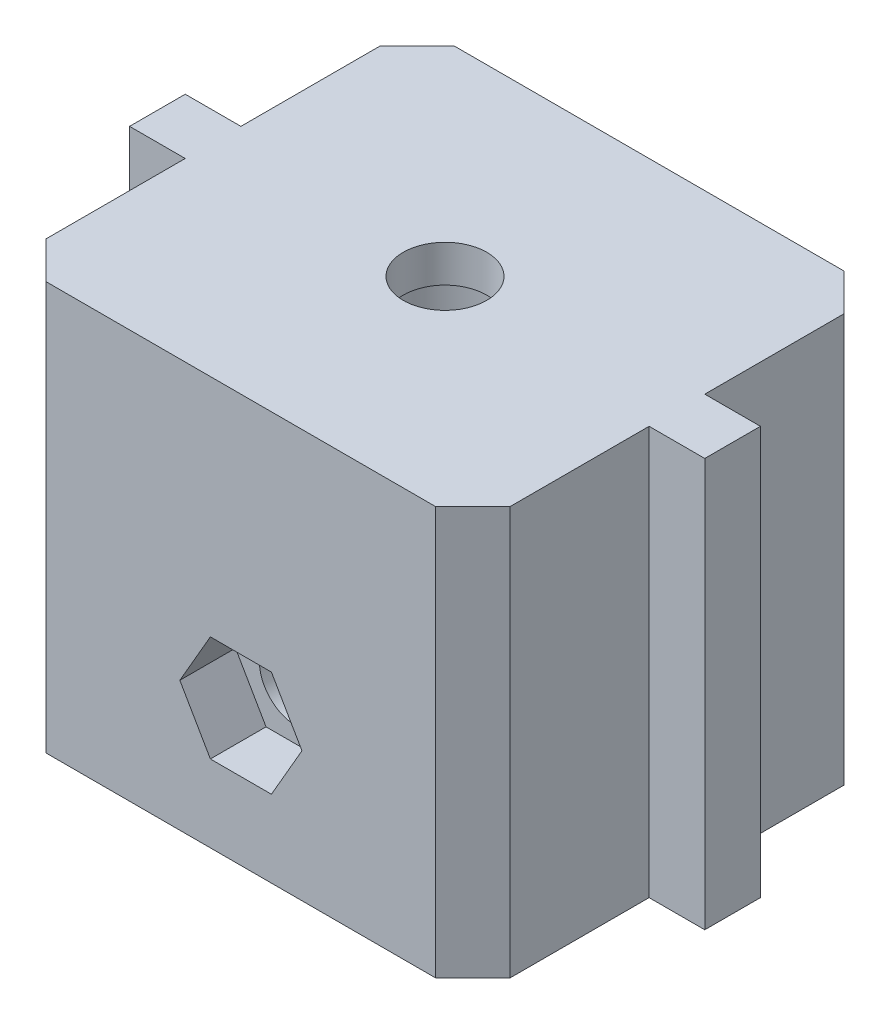
SolidWorks part; units mm, degrees
ref_plane "Front Plane" through (0, 0, 0) normal (0, 0, 1) x (1, 0, 0)
ref_plane "Top Plane" through (0, 0, 0) normal (0, 1, 0) x (1, 0, 0)
ref_plane "Right Plane" through (0, 0, 0) normal (1, 0, 0) x (0, 0, -1)
sketch "Sketch1" plane through (0, 0, 0) normal (0, 1, 0) x (1, 0, 0)
  line L1 (-12.5, -11) -> (12.5, -11)
  line L2 (-12.5, -11) -> (-12.5, 11)
  line L3 (-12.5, 11) -> (12.5, 11)
  line L4 (12.5, -11) -> (12.5, 11)
  line L5 (-12.5, -11) -> (12.5, 11) construction
  line L6 (-12.5, 11) -> (12.5, -11) construction
  point P0 (0, 0)
  dimension "D1" = 22
  dimension "D2" = 25
extrude "Boss-Extrude1" add sketch "Sketch1" along normal blind 22
sketch "Sketch3" plane through (0, 0, 0) normal (0, 1, 0) x (1, 0, 0)
  line L0 (-12.5, 11) -> (-12.5, -11) construction
  line L1 (-15.5, -1.5) -> (15.5, -1.5)
  line L2 (-15.5, -1.5) -> (-15.5, 1.5)
  line L3 (-15.5, 1.5) -> (15.5, 1.5)
  line L4 (15.5, -1.5) -> (15.5, 1.5)
  line L5 (-15.5, -1.5) -> (15.5, 1.5) construction
  line L6 (-15.5, 1.5) -> (15.5, -1.5) construction
  point P0 (0, 0)
  dimension "D1" = 3
  dimension "D2" = 3
extrude "Boss-Extrude2" add sketch "Sketch3" along normal up to surface (22 mm away) up to face at (0, 22, 0)
sketch "Sketch4" plane through (0, 0, 0) normal (0, 1, 0) x (1, 0, 0)
  line L1 (-9.5, 8) -> (9.5, 8)
  line L2 (-9.5, 8) -> (-9.5, -8)
  line L3 (-9.5, -8) -> (9.5, -8)
  line L4 (9.5, 8) -> (9.5, -8)
  line L5 (-9.5, 8) -> (9.5, -8) construction
  line L6 (-9.5, -8) -> (9.5, 8) construction
  point P0 (0, 0)
  dimension "D1" = 19
  dimension "D2" = 16
extrude "Cut-Extrude3" cut sketch "Sketch4" along normal offset from surface (17 mm away) 5 up to face at (0, 22, 0)
sketch "Sketch5" plane through (0, 0, -8) normal (0, 0, -1) x (-1, 0, 0)
  circle A0 centre (0, 7) radius 3
  dimension "D1" = 6
  dimension "D2" = 7
extrude "Boss-Extrude3" add sketch "Sketch5" against normal blind 2.8
sketch "Sketch6" plane through (0, 0, 8) normal (0, 0, -1) x (-1, 0, 0)
  circle A0 centre (0, 7) radius 3
  dimension "D1" = 6
extrude "Boss-Extrude4" add sketch "Sketch6" along normal blind 2.8
sketch "Sketch7" plane through (0, 0, -11) normal (0, 0, -1) x (-1, 0, 0)
  circle A0 centre (0, 7) radius 2
  dimension "D1" = 4
extrude "Cut-Extrude4" cut sketch "Sketch7" against normal through all
chamfer "Chamfer1" distance 3.8 angle 45 2 edges at (-3, 7, 8) (3, 7, -8)
sketch "Sketch8" plane through (0, 0, -11) normal (0, 0, -1) x (-1, 0, 0)
  circle A0 centre (0, 7) radius 3
  dimension "D1" = 6
extrude "Cut-Extrude5" cut sketch "Sketch8" against normal blind 3
sketch "Sketch9" plane through (0, 0, 11) normal (0, 0, 1) x (1, 0, 0)
  line L1 (1.6454, 9.85) -> (-1.6454, 9.85)
  line L2 (-1.6454, 9.85) -> (-3.2909, 7)
  line L3 (-3.2909, 7) -> (-1.6454, 4.15)
  line L4 (-1.6454, 4.15) -> (1.6454, 4.15)
  line L5 (1.6454, 4.15) -> (3.2909, 7)
  line L6 (3.2909, 7) -> (1.6454, 9.85)
  circle A0 centre (0, 7) radius 2.85 construction
  dimension "D1" = 5.7
extrude "Cut-Extrude6" cut sketch "Sketch9" against normal blind 3
chamfer "Chamfer2" distance 2 angle 45 8 edges at (-12.5, 11, -11) (12.5, 11, -11) (12.5, 11, 11) (-12.5, 11, 11) (-9.5, 8.5, -8) (9.5, 8.5, -8) (9.5, 8.5, 8) (-9.5, 8.5, 8)
sketch "Sketch10" plane through (0, 17, 0) normal (0, -1, 0) x (1, 0, 0)
  circle A0 centre (0, 0) radius 3.75
  dimension "D1" = 7.5
extrude "Cut-Extrude7" cut sketch "Sketch10" against normal blind 3
sketch "Sketch11" plane through (0, 20, 0) normal (0, -1, 0) x (1, 0, 0)
  circle A0 centre (0, 0) radius 2.25
  dimension "D1" = 4.5
extrude "Cut-Extrude8" cut sketch "Sketch11" against normal through all
